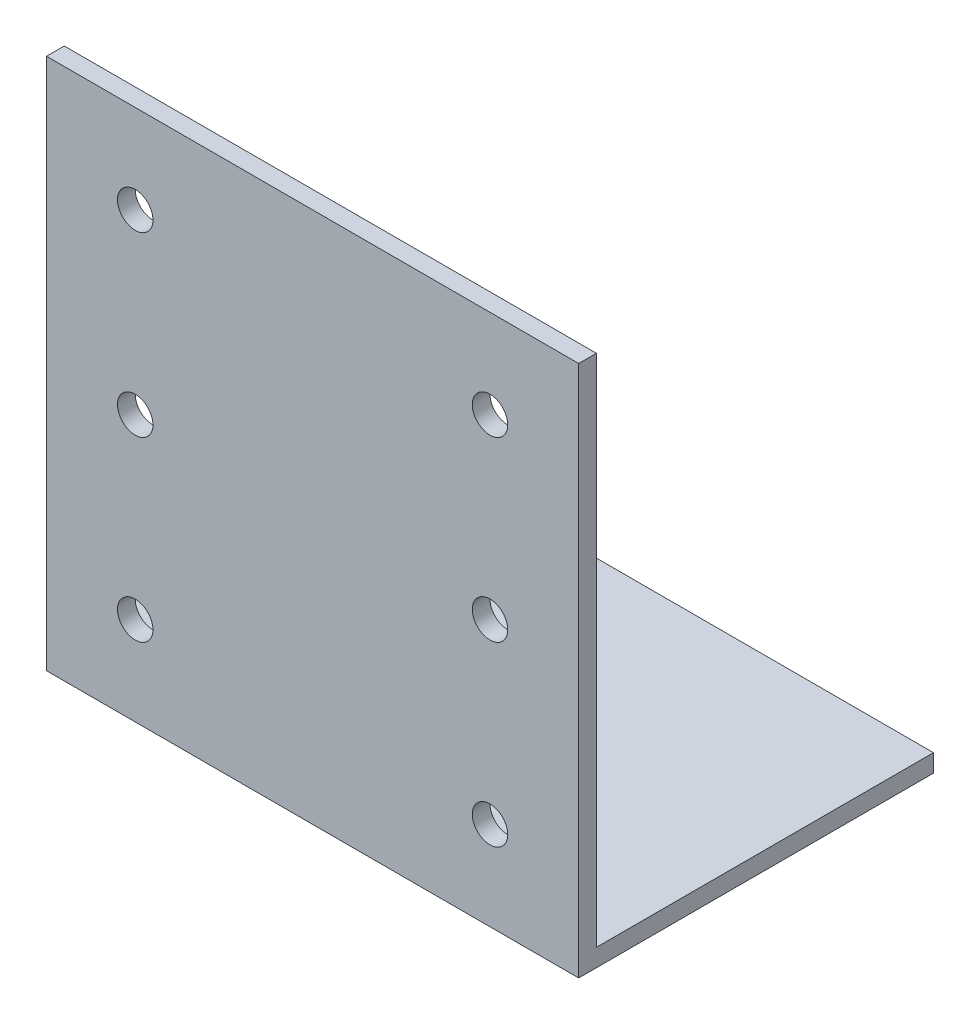
SolidWorks part; units mm, degrees
ref_plane "Спереди" through (0, 0, 0) normal (0, 0, 1) x (1, 0, 0)
ref_plane "Сверху" through (0, 0, 0) normal (0, 1, 0) x (1, 0, 0)
ref_plane "Справа" through (0, 0, 0) normal (1, 0, 0) x (0, 0, -1)
sketch "Эскиз1" plane through (0, 0, 0) normal (1, 0, 0) x (0, 0, -1)
  line L0 (0, 0) -> (0, 60)
  line L1 (0, 0) -> (40, 0)
extrude "Вытянуть-Тонкостенный1" add sketch "Эскиз1" along normal blind 60 thin thin type one direction reverse wall 2
sketch "Эскиз2" plane through (0, 0, 0) normal (0, 0, 1) x (1, 0, 0)
  circle A0 centre (10, 50) radius 2
  circle A1 centre (50, 50) radius 2
  circle A2 centre (50, 30) radius 2
  circle A3 centre (50, 10) radius 2
  circle A5 centre (10, 30) radius 2
  circle A6 centre (10, 10) radius 2
  dimension "D1" = 2
  dimension "D2" = 3
extrude "Вырез-Вытянуть1" cut sketch "Эскиз2" against normal through all
